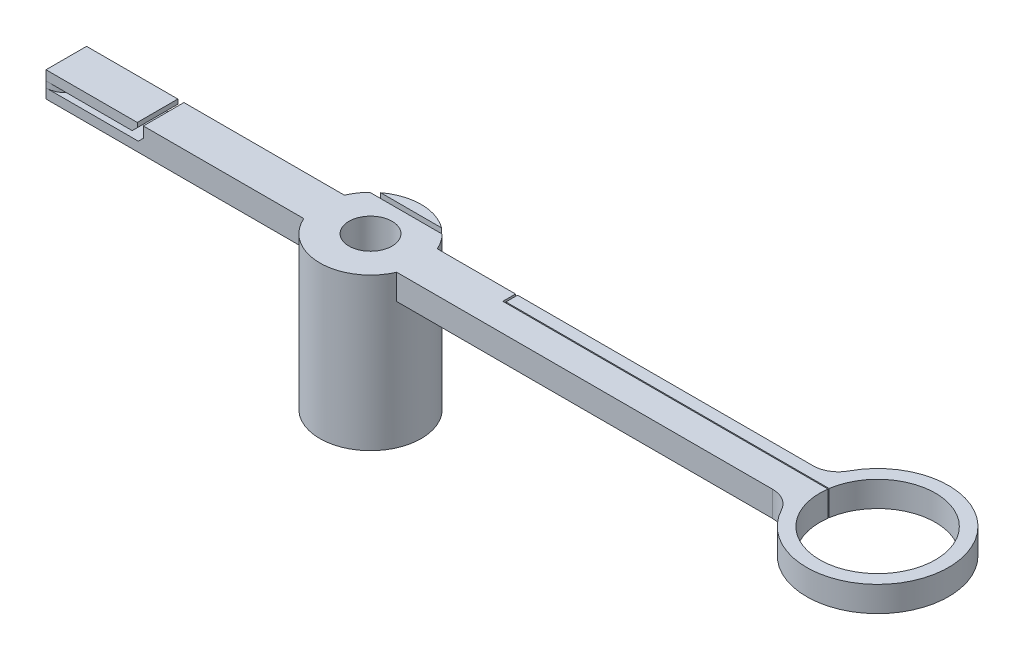
SolidWorks part; units mm, degrees
ref_plane "Спереди" through (0, 0, 0) normal (0, 0, 1) x (1, 0, 0)
ref_plane "Сверху" through (0, 0, 0) normal (0, 1, 0) x (1, 0, 0)
ref_plane "Справа" through (0, 0, 0) normal (1, 0, 0) x (0, 0, -1)
sketch "Эскиз1" plane through (0, 0, 0) normal (0, 1, 0) x (1, 0, 0)
  circle A0 centre (0, 0) radius 11.4
  circle A1 centre (0, 0) radius 14
  dimension "D1" = 22.8
  dimension "D2" = 28
extrude "ring" add sketch "Эскиз1" along normal blind 5
sketch "Эскиз2" plane through (0, 0, 0) normal (0, 1, 0) x (1, 0, 0)
  line L0 (34.0214, 0) -> (-42.1067, 0) construction
  line L1 (-10.7819, 4) -> (-10.7819, -4) construction
  line L2 (-10.7819, 4) -> (-160, 4)
  line L4 (-10.7819, -4) -> (-160, -4)
  line L5 (-160, 4) -> (-160, -4)
  circle A0 centre (0, 0) radius 11.5 construction
  arc A1 (-10.7819, 4) -> (-10.7819, -4) centre (0, 0) ccw
  point P9 (-10.7819, 0)
  dimension "D3" = 23
  dimension "D1" = 160
  dimension "D2" = 8
extrude "stick" add sketch "Эскиз2" along normal blind 5
fillet "Скругление1" radius 5 2 edges at (-13.4164, 2.5, 4) (-13.4164, 2.5, -4)
sketch "Эскиз5" plane through (0, 0, 0) normal (0, -1, 0) x (1, 0, 0)
  line L0 (0, 0) -> (-70.3859, 0) construction
  line L1 (-75.4, -4) -> (-75.4, -1.5)
  line L3 (-75.4, -1.5) -> (0, -1.5)
  line L4 (0, -1.5) -> (0, -1.7)
  line L5 (0, -1.7) -> (-75, -1.7)
  line L6 (-75, -1.7) -> (-75, -4)
  line L7 (-75, -4) -> (-75.4, -4)
  line L8 (-16.7332, -4) -> (-160, -4) construction
  dimension "D1" = 0.2
  dimension "D2" = 0.4
  dimension "D3" = 75
  dimension "D4" = 1.5
extrude "correction hole 1" cut sketch "Эскиз5" against normal through all
sketch "Эскиз9" plane through (0, 0, 4) normal (0, 0, 1) x (1, 0, 0)
  line L0 (-142, 5) -> (-142, 4.1)
  line L1 (-160, 5) -> (-16.7332, 5) construction
  line L2 (-143, 3.1) -> (-156, 3.1)
  line L3 (-156, 3.1) -> (-156, 1.9)
  line L4 (-156, 1.9) -> (-141.8, 1.9)
  line L5 (-140.8, 2.9) -> (-140.8, 5)
  line L6 (-140.8, 5) -> (-142, 5)
  line L7 (-160, 5) -> (-160, 0) construction
  line L8 (-142, 4.1) -> (-143, 3.1)
  line L9 (-141.8, 1.9) -> (-140.8, 2.9)
  point P1 (-142, 3.1)
  point P4 (-160, 2.5)
  point P7 (-140.8, 1.9)
  point P9 (-156, 2.5)
  dimension "D1" = 1.2
  dimension "D2" = 4
  dimension "D3" = 14
  dimension "D6" = 1
  dimension "D7" = 1
extrude "Вытянуть1" cut sketch "Эскиз9" against normal up to next
fillet "Скругление2" radius 4 2 edges at (-156, 2.5, -4) (-156, 2.5, 4)
sketch "Эскиз10" plane through (0, 5, 0) normal (0, 1, 0) x (1, 0, 0)
  circle A0 centre (-100, 0) radius 10
  dimension "D1" = 20
  dimension "D2" = 100
extrude "Вытянуть2" add sketch "Эскиз10" against normal blind 30
sketch "Эскиз11" plane through (0, -25, 0) normal (0, -1, 0) x (1, 0, 0)
  circle A0 centre (-100, 0) radius 4.25
  circle A3 centre (-100, 0) radius 10 construction
  dimension "D1" = 8.5
extrude "Вытянуть3" cut sketch "Эскиз11" against normal blind 30
sketch "Эскиз12" plane through (0, -25, 0) normal (0, -1, 0) x (1, 0, 0)
  line L1 (-107.1414, -7) -> (-92.8586, -7)
  line L2 (-107.1414, -7) -> (-107.1414, -8)
  line L3 (-107.1414, -8) -> (-92.8586, -8)
  line L4 (-92.8586, -7) -> (-92.8586, -8)
  circle A0 centre (-100, 0) radius 10 construction
  point P6 (-100, -7)
  point P7 (-100, 0)
  dimension "D1" = 1
  dimension "D2" = 7
extrude "Вытянуть4" cut sketch "Эскиз12" against normal blind 5
sketch "Эскиз13" plane through (0, 5, 0) normal (0, 1, 0) x (1, 0, 0)
  line L0 (-94, 8) -> (-106, 8) construction
  line L1 (-107.1414, 8) -> (-92.8586, 8)
  line L2 (-107.1414, 8) -> (-107.1414, 7)
  line L3 (-107.1414, 7) -> (-92.8586, 7)
  line L4 (-92.8586, 8) -> (-92.8586, 7)
  arc A1 (-90.8348, 4) -> (-109.1652, 4) centre (-100, 0) ccw construction
extrude "Вытянуть6" cut sketch "Эскиз13" against normal blind 5
